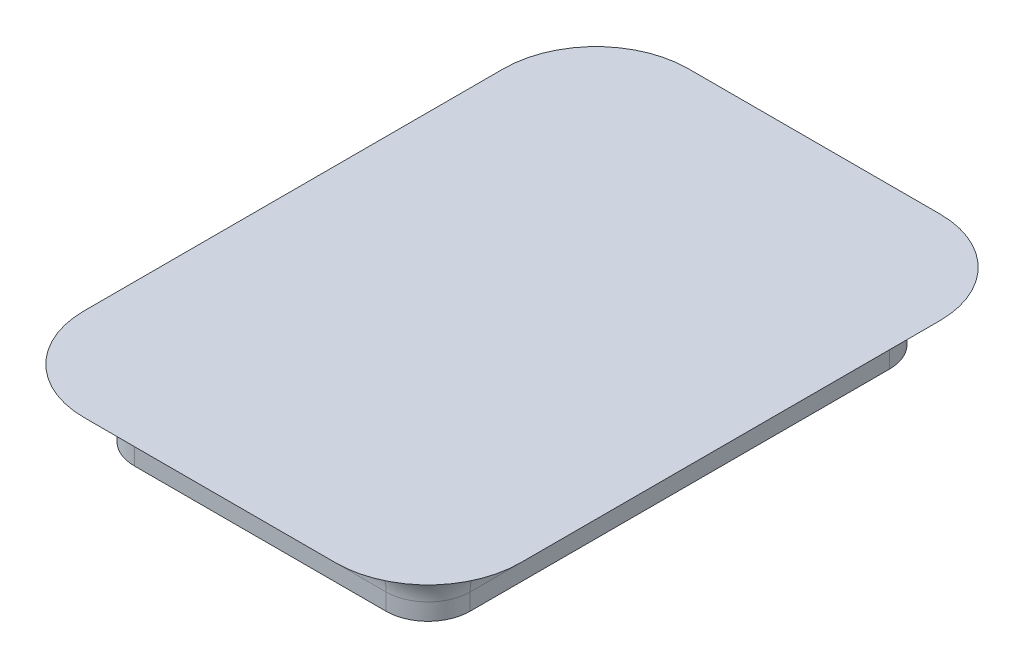
SolidWorks part; units mm, degrees
ref_plane "Plane1" through (0, 0, 0) normal (0, 0, 1) x (1, 0, 0)
ref_plane "Plane2" through (0, 0, 0) normal (0, 1, 0) x (1, 0, 0)
ref_plane "Plane3" through (0, 0, 0) normal (1, 0, 0) x (0, 0, -1)
sketch "Sketch1" plane through (0, 0, 0) normal (0, 0, 1) x (1, 0, 0)
  line L0 (-25, 5) -> (25, 5)
  line L1 (-25, 5) -> (-25, 0)
  line L2 (25, 0) -> (-25, 0)
  line L3 (25, 0) -> (25, 5)
  line L4 (0, 5) -> (0, 0) construction
  line L5 (50, 0) -> (-50, 0) construction
  dimension "D1" = 50
  dimension "D2" = 5
extrude "Base-Extrude" add sketch "Sketch1" along normal mid plane 50
sketch "Sketch3" plane through (0, 0, 0) normal (0, 0, 1) x (1, 0, 0)
  line L0 (0, 0) -> (0, -4) construction
  line L1 (-10, 0) -> (10, 0)
  line L2 (-10, 0) -> (-10, -4)
  line L3 (10, -4) -> (-10, -4)
  line L4 (10, -4) -> (10, 0)
  line L5 (25, 0) -> (-25, 0) construction
  dimension "Depth" = 20
  dimension "Height" = 4
extrude "Boss-Extrude1" add sketch "Sketch3" along normal mid plane 30
fillet "Fillet1" radius 2.5 4 edges at (10, -2, 15) (-10, -2, 15) (-10, -2, -15) (10, -2, -15)
fillet "Fillet2" radius 3 8 edges at (-10, 0, 0) (-9.2678, 0, 14.2678) (-9.2678, 0, -14.2678) (0, 0, 15) (0, 0, -15) (9.2678, 0, 14.2678) (9.2678, 0, -14.2678) (10, 0, 0)
sketch "Sketch4" plane through (25, 0, 0) normal (1, 0, 0) x (0, 0, -1)
  line L4 (25, 5) -> (-25, 5)
  line L5 (-25, 5) -> (-25, 0)
  line L6 (-25, 0) -> (25, 0)
  line L7 (25, 0) -> (25, 5)
  line L8 (25, 5) -> (-25, 5)
  line L9 (-25, 5) -> (-25, 0)
  line L10 (-25, 0) -> (25, 0)
  line L11 (25, 0) -> (25, 5)
  dimension "D1" = 0
extrude "Cut-Extrude1" cut sketch "Sketch4" against normal through all
sketch "Orientation sketch" plane through (0, 0, 0) normal (0, 1, 0) x (-1, 0, 0)
  line L4 (-7.5, -18) -> (7.5, -18)
  line L5 (13, -12.5) -> (13, 12.5)
  line L6 (7.5, 18) -> (-7.5, 18)
  line L7 (-13, 12.5) -> (-13, -12.5)
  line L8 (-7.5, -18) -> (7.5, -18)
  line L9 (13, -12.5) -> (13, 12.5)
  line L10 (7.5, 18) -> (-7.5, 18)
  line L11 (-13, 12.5) -> (-13, -12.5)
  arc A4 (-13, -12.5) -> (-7.5, -18) centre (-7.5, -12.5) ccw
  arc A5 (7.5, -18) -> (13, -12.5) centre (7.5, -12.5) ccw
  arc A6 (13, 12.5) -> (7.5, 18) centre (7.5, 12.5) ccw
  arc A7 (-7.5, 18) -> (-13, 12.5) centre (-7.5, 12.5) ccw
  arc A8 (-13, -12.5) -> (-7.5, -18) centre (-7.5, -12.5) ccw
  arc A9 (7.5, -18) -> (13, -12.5) centre (7.5, -12.5) ccw
  arc A10 (13, 12.5) -> (7.5, 18) centre (7.5, 12.5) ccw
  arc A11 (-7.5, 18) -> (-13, 12.5) centre (-7.5, 12.5) ccw
  dimension "D1" = 0
